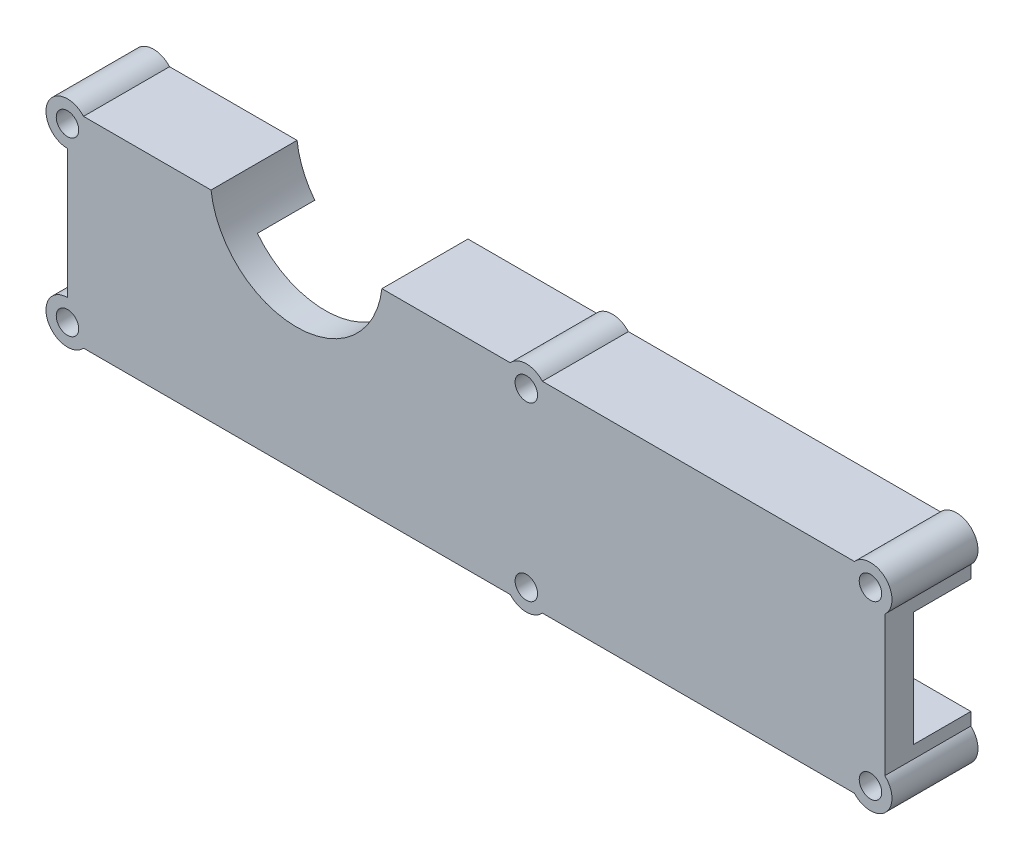
SolidWorks part; units mm, degrees
material "Nylon 101"
ref_plane "Front Plane" through (0, 0, 0) normal (0, 0, 1) x (1, 0, 0)
ref_plane "Top Plane" through (0, 0, 0) normal (0, 1, 0) x (1, 0, 0)
ref_plane "Right Plane" through (0, 0, 0) normal (1, 0, 0) x (0, 0, -1)
sketch "Sketch1" plane through (0, 0, 0) normal (0, 0, 1) x (1, 0, 0)
  line L0 (0, 38.1) -> (76.2, 38.1) construction
  line L1 (3.5498, -3.175) -> (72.6502, -3.175)
  line L3 (3.5498, 41.275) -> (72.6502, 41.275)
  line L4 (79.375, 3.5498) -> (79.375, 34.5502)
  line L5 (76.2, 0) -> (76.2, 38.1) construction
  line L6 (0, 0) -> (76.2, 0) construction
  line L8 (-3.175, 41.275) -> (79.375, 41.275) construction
  line L9 (-3.175, -3.175) -> (-3.175, 41.275) construction
  line L10 (-3.175, -3.175) -> (79.375, -3.175) construction
  line L11 (79.375, -3.175) -> (79.375, 41.275) construction
  line L12 (-3.5498, 41.275) -> (-31.9729, 41.275)
  line L13 (0, 0) -> (-101.6, 0) construction
  line L15 (0, 38.1) -> (-101.6, 38.1) construction
  line L17 (-101.6, 4.7625) -> (-101.6, 33.3375)
  line L18 (-98.0502, -3.175) -> (-3.5498, -3.175)
  line L19 (-69.8127, 41.275) -> (-98.0502, 41.275)
  line L20 (0, 0) -> (0, 38.1) construction
  circle A4 centre (0, 38.1) radius 2.4892
  circle A5 centre (0, 0) radius 2.4892
  circle A6 centre (76.2, 38.1) radius 2.4892
  circle A7 centre (76.2, 0) radius 2.4892
  arc A8 (3.5498, 41.275) -> (-3.5498, 41.275) centre (0, 38.1) ccw
  arc A9 (-3.5498, -3.175) -> (3.5498, -3.175) centre (0, 0) ccw
  circle A10 centre (76.2, 0) radius 4.7625
  circle A11 centre (76.2, 38.1) radius 4.7625
  circle A12 centre (-101.6, 38.1) radius 2.4892
  circle A14 centre (-101.6, 0) radius 2.4892
  arc A15 (-98.0502, 41.275) -> (-101.6, 33.3375) centre (-101.6, 38.1) ccw
  arc A16 (-101.6, 4.7625) -> (-98.0502, -3.175) centre (-101.6, 0) ccw
  arc A17 (-69.8127, 41.275) -> (-31.9729, 41.275) centre (-50.8928, 43.4975) ccw
  point P20 (-35.5701, 19.05)
  dimension "D3" = 4.9784
  dimension "D5" = 9.525
  dimension "D7" = 38.1
  dimension "D1" = 38.1
  dimension "D2" = 76.2
  dimension "D6" = 101.6
  dimension "D8" = 50.8928
  dimension "D9" = 5.3975
  dimension "D4" = 3.175
extrude "Boss-Extrude1" add sketch "Sketch1" along normal blind 19.05 contours L1 L4 L3 A7 A6 A5 A4 | A8 A4 | A9 A5 | A10 A7 | A11 A6 region at (-10.3593, 18.0645, 0) region at (72.9277, 3.2723, 0) region at (72.9277, 34.8277, 0)
sketch "Sketch2" plane through (-101.6, 0, 0) normal (-1, 0, 0) x (0, 0, 1)
  line L0 (0, 4.7625) -> (0, 33.3375) construction
  line L16 (0, 31.75) -> (0, 6.35)
  line L17 (0, 6.35) -> (12.7, 6.35)
  line L18 (12.7, 6.35) -> (12.7, 31.75)
  line L19 (12.7, 31.75) -> (0, 31.75)
  point P3 (0, 19.05)
  point P9 (0, 19.05)
  dimension "D1" = 12.7
  dimension "D2" = 25.4
extrude "Cut-Extrude1" cut sketch "Sketch2" against normal through all
